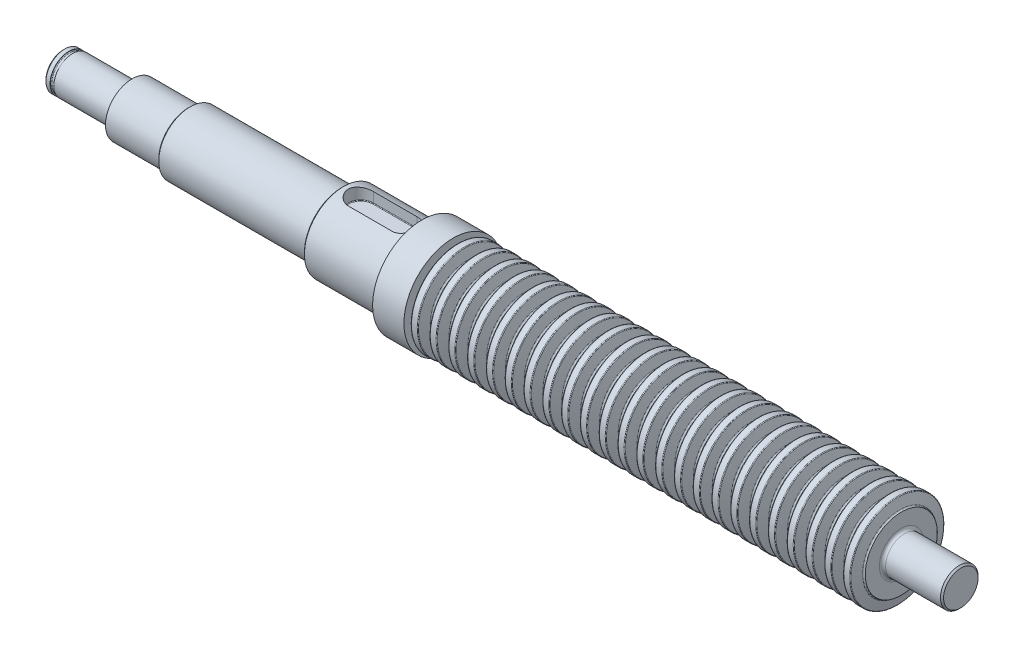
SolidWorks part; units mm, degrees
material "Сталь 45 ГОСТ 535-88"
ref_plane "Спереди" through (0, 0, 0) normal (0, 0, 1) x (1, 0, 0)
ref_plane "Сверху" through (0, 0, 0) normal (0, 1, 0) x (1, 0, 0)
ref_plane "Слева" through (0, 0, 0) normal (1, 0, 0) x (0, 0, -1)
sketch "Эскиз1" plane through (0, 0, 0) normal (0, 0, 1) x (1, 0, 0)
  line L0 (-119.5, 0) -> (-119.5, 6)
  line L1 (-119.5, 6) -> (-97.5, 6)
  line L2 (-79.5, 8.5) -> (-79.5, 10)
  line L3 (-79.5, 10) -> (-30.5, 10)
  line L4 (-30.5, 10) -> (-30.5, 12.5)
  line L5 (-30.5, 12.5) -> (-5, 12.5)
  line L6 (-5, 12.5) -> (-5, 15.75)
  line L7 (-5, 15.75) -> (5, 15.75)
  line L8 (5, 15.75) -> (5, 11.5)
  line L9 (5, 11.5) -> (148, 11.5)
  line L10 (148, 11.5) -> (148, 6)
  line L11 (148, 6) -> (167, 6)
  line L12 (167, 6) -> (167, 0)
  line L13 (167, 0) -> (-119.5, 0)
  line L14 (167, 0) -> (187.422, 0) construction
  line L15 (-79.5, 8.5) -> (-97.5, 8.5)
  line L16 (-97.5, 8.5) -> (-97.5, 6)
  point P0 (0, 15.75)
  dimension "D1" = 12
  dimension "D2" = 23
  dimension "D3" = 10
  dimension "D4" = 31.5
  dimension "D5" = 25
  dimension "D6" = 20.0001
  dimension "D7" = 143
  dimension "D8" = 19
  dimension "D9" = 25.5
  dimension "D10" = 49
  dimension "D11" = 40
  dimension "D12" = 286.5
  dimension "D13" = 12
  dimension "D14" = 18
  dimension "D15" = 17
revolve "Повернуть1" add sketch "Эскиз1" angle 360 about L14
cosmetic thread "Условное изображение резьбы1" parameters "D2"=20
sketch "Эскиз2" plane through (0, 0, 0) normal (0, 0, 1) x (1, 0, 0)
  line L0 (7.58, 11.5) -> (7.58, 15.5639) construction
  line L1 (-5, 15.75) -> (-5, -15.75) construction
  line L2 (6.6738, 15) -> (8.4862, 15)
  line L3 (8.7277, 14.8147) -> (9.5166, 11.8706)
  line L4 (9.9996, 11.5) -> (5.1604, 11.5)
  line L5 (148, 11.5) -> (5, 11.5) construction
  line L6 (6.4323, 14.8147) -> (5.6434, 11.8706)
  line L7 (0, 0) -> (20.4257, 0) construction
  line L8 (167, 0) -> (-119.5, 0) construction
  line L9 (6.08, 13.5) -> (9.08, 13.5) construction
  arc A0 (8.4862, 15) -> (8.7277, 14.8147) centre (8.4862, 14.75) cw
  arc A1 (6.4323, 14.8147) -> (6.6738, 15) centre (6.6738, 14.75) cw
  arc A2 (9.5166, 11.8706) -> (9.9996, 11.5) centre (9.9996, 12) ccw
  arc A3 (5.1604, 11.5) -> (5.6434, 11.8706) centre (5.1604, 12) ccw
  point P12 (7.58, 15)
  point P14 (8.6781, 15)
  point P17 (6.4819, 15)
  point P20 (9.6159, 11.5)
  point P23 (5.5441, 11.5)
  dimension "D2" = 0.25
  dimension "D3" = 0.5
  dimension "D1" = 30
  dimension "D5" = 30
  dimension "D6" = 1.5
  dimension "D7" = 3
  dimension "D8" = 12.58
sketch "Эскиз3" plane through (5, 0, 0) normal (1, 0, 0) x (0, 0, -1)
  circle A0 centre (0, 0) radius 15
curve "Спираль1" pitch 6 height 143 turns 23.8333
sweep "Tr30x6-6e" [suppressed] add profiles "Эскиз2" path "Спираль1"
revolve "Повернуть2" add sketch "Эскиз2<2>" angle 360 about L7
sketch "Эскиз2<2>" plane through (0, 0, 0) normal (0, 0, 1) x (1, 0, 0) same geometry as "Эскиз2"
pattern_linear "Линейный массив1" count 24 spacing 6 along (1, 0, 0) of "Повернуть2"
sketch "Эскиз4" plane through (0, 0, 0) normal (0, 0, 1) x (1, 0, 0)
  line L0 (167, 6) -> (148, 6)
  line L1 (167, 6) -> (167, 15)
  line L2 (148, 6) -> (148, 15)
  line L3 (167, 15) -> (148, 15)
  line L4 (167, 0) -> (187.422, 0) construction
  dimension "D1" = 30
fillet "Скругление3" radius 1 4 edges at (148, 0, 6) (-5, 0, 12.5) (-30.5, 0, 10) (-97.5, 0, 6)
chamfer "Фаска1" distance 0.5 angle 45 4 edges at (-119.5, 0, 6) (167, 0, 6) (-79.5, 0, 10) (-30.5, 0, 12.5)
ref_plane "Плоскость1" through (167.5, 0, 0) normal (0, -1, 0) x (0, 0, 1)
fillet "Скругление6" radius 0.5 1 edges at (-79.5, 0, 8.5)
sketch "Эскиз6" plane through (167.5, 0, 0) normal (0, -1, 0) x (0, 0, 1)
  line L0 (5.9, 284) -> (7, 284)
  line L1 (7, 284) -> (7, 285.2)
  line L2 (7, 285.2) -> (5.9, 285.2)
  line L3 (5.65, 284.95) -> (5.65, 284.25)
  line L4 (0, 0.5) -> (0, 303.3551) construction
  line L5 (-5.5, 0.5) -> (5.5, 0.5) construction
  line L6 (10, 247) -> (-10, 247) construction
  line L7 (-6, 286.5) -> (6, 286.5) construction
  arc A0 (5.65, 284.25) -> (5.9, 284) centre (5.9, 284.25) ccw
  arc A1 (5.65, 284.95) -> (5.9, 285.2) centre (5.9, 284.95) cw
  dimension "D1" = 0.25
  dimension "D2" = 0.25
  dimension "D3" = 37
  dimension "D4" = 1.2
  dimension "D5" = 11.3
  dimension "D6" = 14
  dimension "D7" = 1.3
revolve "Канавка для DIN 6799 - 10, Замковое кольцо для вала1" cut sketch "Эскиз6"
sketch "Эскиз7" plane through (0, 0, 0) normal (0, 1, 0) x (1, 0, 0)
  line L0 (0, 0) -> (-17.5, 0) construction
  line L1 (-5, 15.75) -> (-5, -15.75) construction
  line L2 (-24.5, -4) -> (-10.5, -4)
  line L3 (-24.5, -4) -> (-24.5, 4) construction
  line L4 (-24.5, 4) -> (-10.5, 4)
  line L5 (-10.5, -4) -> (-10.5, 4) construction
  line L6 (-24.5, -4) -> (-10.5, 4) construction
  line L7 (-24.5, 4) -> (-10.5, -4) construction
  line L9 (-30.5, 11.0001) -> (-30.5, -11.0001) construction
  arc A0 (-24.5, 4) -> (-24.5, -4) centre (-24.5, 0) ccw
  arc A1 (-10.5, -4) -> (-10.5, 4) centre (-10.5, 0) ccw
  dimension "D1" = 22
  dimension "D4" = 2
  dimension "D2" = 8
  dimension "D3" = 12.5
extrude "Шпоночный паз под ЗК" cut sketch "Эскиз7" along normal up to surface (3.3427 mm away) from offset 8.5 up to face at (-30, 0, -12.5)
fillet "Скругление5" radius 0.2 4 edges at (-6.5, 8.5, 0) (-17.5, 8.5, 4) (-28.5, 8.5, 0) (-17.5, 8.5, -4)
